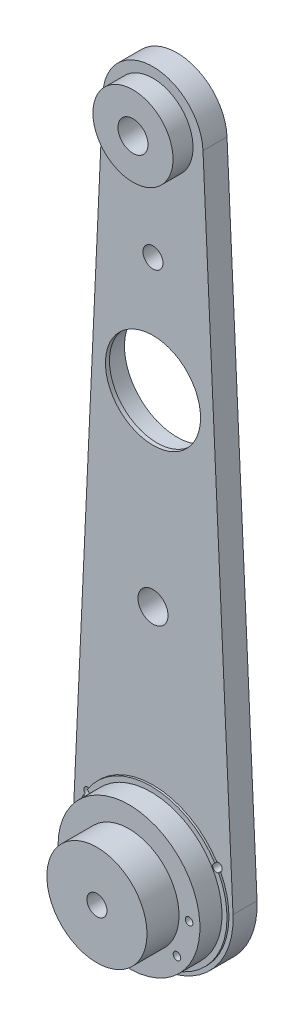
SolidWorks part; units mm, degrees
ref_plane "Front Plane" through (0, 0, 0) normal (0, 0, 1) x (1, 0, 0)
ref_plane "Top Plane" through (0, 0, 0) normal (0, 1, 0) x (1, 0, 0)
ref_plane "Right Plane" through (0, 0, 0) normal (1, 0, 0) x (0, 0, -1)
sketch "Sketch1" plane through (0, 0, 0) normal (0, 0, 1) x (1, 0, 0)
  line L0 (0, 205.4835) -> (0, 0) construction
  line L1 (25.3727, 1.1774) -> (15.8579, 206.2193)
  line L2 (-15.8579, 206.2193) -> (-25.3727, 1.1774)
  circle A1 centre (0, 205.4835) radius 4.7625
  arc A2 (-15.8579, 206.2193) -> (15.8579, 206.2193) centre (0, 205.4835) cw
  arc A3 (-25.3727, 1.1774) -> (25.3727, 1.1774) centre (0, 0) ccw
  dimension "D2" = 15.875
  dimension "D3" = 25.4
  dimension "D4" = 9.525
  dimension "D1" = 205.4835
extrude "Boss-Extrude1" add sketch "Sketch1" along normal mid plane 7.62
sketch "Sketch2" plane through (0, 0, 3.81) normal (0, 0, 1) x (1, 0, 0)
  circle A0 centre (0, 0) radius 22.5
  dimension "D1" = 45
extrude "Boss-Extrude2" add sketch "Sketch2" along normal blind 7.62
sketch "Sketch3" plane through (0, 0, 3.81) normal (0, 0, 1) x (1, 0, 0)
  circle A0 centre (0, 0) radius 24.0899
extrude "Boss-Extrude3" add sketch "Sketch3" along normal offset from surface (0.62 mm away) 7 up to face at (22.5, 0, 11.43)
sketch "Sketch4" plane through (0, 0, 3.81) normal (0, 0, 1) x (1, 0, 0)
  circle A0 centre (0, 73.0199) radius 4.7625
  circle A1 centre (0, 132.4635) radius 16.6688
  circle A2 centre (0, 205.4835) radius 4.7625 construction
  dimension "D2" = 9.525
  dimension "D3" = 33.3375
  dimension "D1" = 73.0199
  dimension "D4" = 73.0199
extrude "Cut-Extrude1" cut sketch "Sketch4" against normal through all both and the other way through all
sketch "Sketch5" plane through (0, 0, 0) normal (0, 0, 1) x (1, 0, 0)
  line L0 (-155.5635, 72.3706) -> (0, 227.9341)
  line L1 (-155.5635, 72.3706) -> (0, -83.1929)
  line L2 (0, 227.9341) -> (155.5635, 72.3706)
  line L3 (0, -83.1929) -> (155.5635, 72.3706)
  line L4 (-155.5635, 72.3706) -> (155.5635, 72.3706) construction
  line L5 (0, 227.9341) -> (0, -83.1929) construction
  arc A1 (15.8579, 206.2193) -> (-15.8579, 206.2193) centre (0, 205.4835) ccw construction
  point P1 (0, 72.3706)
  dimension "D1" = 220
sketch "Sketch6" plane through (0, 0, 3.81) normal (0, 0, 1) x (1, 0, 0)
  circle A0 centre (0, 132.4635) radius 16.6688
  circle A1 centre (0, 132.4635) radius 15.0813
  circle A2 centre (0, 132.4635) radius 16.6688 construction
  dimension "D1" = 1.5875
extrude "Boss-Extrude4" add sketch "Sketch6" against normal offset from surface (1.27 mm away) 6.35 up to face at (4.7625, 73.0199, -3.81)
sketch "Sketch7" plane through (0, 0, -3.81) normal (0, 0, -1) x (-1, 0, 0)
  line L0 (11, -20.6542) -> (11, 7.5625) construction
  line L1 (-11.7938, -25.4) -> (11.7937, -25.4)
  line L2 (-11.7938, -25.4) -> (-11.7938, 8.3563)
  line L3 (-11.7938, 8.3563) -> (11.7937, 8.3563)
  line L4 (11.7937, -25.4) -> (11.7937, 8.3563)
  line L5 (-11.7938, -25.4) -> (11.7937, 8.3563) construction
  line L6 (-11.7938, 8.3563) -> (11.7937, -25.4) construction
  line L7 (11, 7.5625) -> (-11, 7.5625) construction
  arc A0 (-25.3727, 1.1774) -> (25.3727, 1.1774) centre (0, 0) ccw construction
  point P0 (0, -8.5219)
  dimension "D1" = 0.7937
  dimension "D2" = 0.7937
extrude "Cut-Extrude2" cut sketch "Sketch7" against normal blind 1.5875
sketch "Sketch8" plane through (0, 0, -2.2225) normal (0, 0, -1) x (-1, 0, 0)
  circle A0 centre (-9, 5.5625) radius 0.95
  circle A1 centre (9, 5.5625) radius 0.95
  circle A2 centre (9, -5.5625) radius 0.95
  circle A3 centre (-9, -5.5625) radius 0.95
  dimension "D1" = 1.9
extrude "Cut-Extrude3" cut sketch "Sketch8" against normal through all
sketch "Sketch9" plane through (0, 0, 3.81) normal (0, 0, 1) x (1, 0, 0)
  circle A0 centre (0, 205.4835) radius 12.7
  circle A1 centre (0, 205.4835) radius 4.7625 construction
  circle A2 centre (0, 205.4835) radius 4.7625
  dimension "D1" = 25.4
extrude "Boss-Extrude5" add sketch "Sketch9" along normal blind 6.35
sketch "Sketch10" plane through (0, 0, 11.43) normal (0, 0, 1) x (1, 0, 0)
  circle A0 centre (0, 0) radius 15.875
  dimension "D1" = 31.75
extrude "Boss-Extrude6" add sketch "Sketch10" along normal blind 10.16
sketch "Sketch11" plane through (0, 0, -3.81) normal (0, 0, -1) x (-1, 0, 0)
  circle A0 centre (-20.7431, 11.983) radius 1.2
  circle A1 centre (20.7431, 11.983) radius 1.2
  circle A2 centre (19.0618, 0) radius 1.2
  circle A3 centre (15.2212, -11.4747) radius 1.2
  circle A4 centre (-15.2212, -11.4747) radius 1.2
  circle A5 centre (-19.0618, 0) radius 1.2
  dimension "D1" = 2.4
extrude "Cut-Extrude4" cut sketch "Sketch11" against normal through all both and the other way through all
sketch "Sketch12" plane through (0, 0, 3.81) normal (0, 0, 1) x (1, 0, 0)
  line L3 (0, 132.4635) -> (0, 205.4835) construction
  circle A7 centre (0, 132.4635) radius 15.0813 construction
  circle A8 centre (0, 205.4835) radius 4.7625 construction
  circle A9 centre (0, 168.9735) radius 3.175
  dimension "D1" = 6.35
extrude "Cut-Extrude5" cut sketch "Sketch12" against normal through all
sketch "Sketch13" plane through (0, 0, -2.2225) normal (0, 0, -1) x (-1, 0, 0)
  circle A0 centre (0, 0) radius 3.175
  dimension "D1" = 6.35
extrude "Cut-Extrude6" cut sketch "Sketch13" against normal through all both and the other way through all
sketch "Sketch14" plane through (0, 0, -2.2225) normal (0, 0, -1) x (-1, 0, 0)
  circle A0 centre (0, 0) radius 4
  dimension "D1" = 8
extrude "Cut-Extrude7" cut sketch "Sketch14" against normal blind 12.7
equation "\"UpperLinkLength\"= \"LowerFirstStage\" + \"LowerSecondStage\""
equation "\"LowerFirstStage\"= \"60T_20T_171B\""
equation "\"LowerSecondStage\"= \"60T_20T_113B\""
equation "\"D1@Sketch1\"=\"UpperLinkLength\""
equation "\"UpperStage\"= \"60T_20T_113B\""
equation "\"60T_20T_113B\"= 2.8748"
equation "\"60T_20T_171B\"= 5.2151"
equation "\"D1@Sketch4\"=\"UpperStage\""
equation "\"D4@Sketch4\"=\"LowerSecondStage\""
